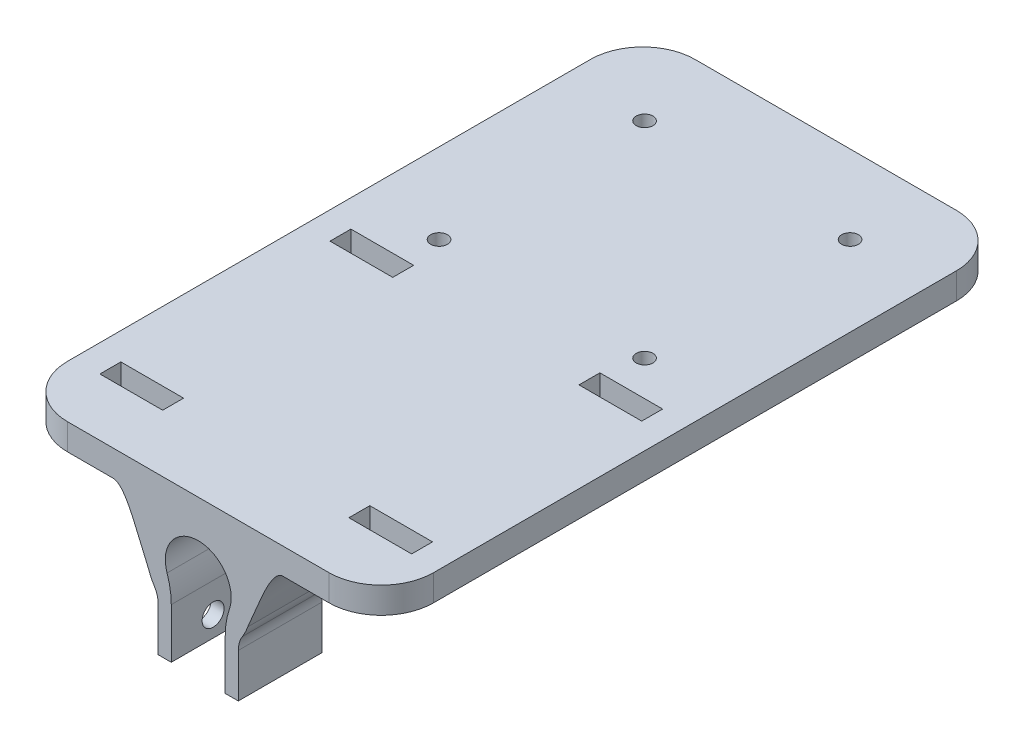
SolidWorks part; units mm, degrees
ref_plane "Front Plane" through (0, 0, 0) normal (0, 0, 1) x (1, 0, 0)
ref_plane "Top Plane" through (0, 0, 0) normal (0, 1, 0) x (1, 0, 0)
ref_plane "Right Plane" through (0, 0, 0) normal (1, 0, 0) x (0, 0, -1)
sketch "Sketch3" plane through (0, 0, 0) normal (0, 0, 1) x (1, 0, 0)
  line L0 (0, 11) -> (0, 0) construction
  line L1 (-35, 13.5) -> (35, 13.5)
  line L2 (-35, 13.5) -> (-35, 8.5)
  line L3 (-35, 8.5) -> (35, 8.5)
  line L4 (35, 13.5) -> (35, 8.5)
  line L5 (-35, 13.5) -> (35, 8.5) construction
  line L6 (-35, 8.5) -> (35, 13.5) construction
  point P0 (0, 11)
  dimension "D1" = 5
  dimension "D2" = 70
  dimension "D3" = 11
extrude "Boss-Extrude2" add sketch "Sketch3" along normal blind 120 from offset 10
sketch "Sketch1" plane through (0, 0, 0) normal (0, 0, 1) x (1, 0, 0)
  line L0 (-35, 8.5) -> (35, 8.5) construction
  line L1 (0, 0) -> (0, -9) construction
  line L2 (-16.0979, 8.5) -> (16.0979, 8.5)
  line L3 (0, 0) -> (-7.6604, -6.4279) construction
  line L5 (5.1604, -16.4279) -> (5.1604, -6.8736)
  line L6 (-6.1604, -16.4279) -> (-5.1604, -16.4279)
  line L7 (-6.1604, -16.4279) -> (-7.6604, -16.4279)
  line L8 (-5.1604, -16.4279) -> (-5.1604, -6.8736)
  line L9 (-7.6604, -16.4279) -> (-7.6604, -8.0444)
  line L10 (6.1604, -16.4279) -> (7.6604, -16.4279)
  line L11 (6.1604, -16.4279) -> (5.1604, -16.4279)
  line L12 (7.6604, -16.4279) -> (7.6604, -8.0444)
  arc A0 (5.9629, -2.033) -> (-5.9629, -2.033) centre (0, 0) ccw
  arc A1 (8.4403, -5.363) -> (9.4524, -3.2639) centre (0, 0) ccw
  arc A2 (-7.6604, -8.0444) -> (-8.4403, -5.363) centre (-12.6604, -8.0444) ccw
  arc A3 (-5.1604, -6.8736) -> (-5.9629, -2.033) centre (-20.1604, -6.8736) ccw
  arc A4 (5.1604, -6.8736) -> (5.9629, -2.033) centre (20.1604, -6.8736) cw
  arc A5 (7.6604, -8.0444) -> (8.4403, -5.363) centre (12.6604, -8.0444) cw
  arc A6 (-9.4524, -3.2639) -> (-8.4403, -5.363) centre (0, 0) ccw
  spline S0 degree 3 poles (-16.0979, 8.5) (-13.7253, 8.1529) (-11.6393, 1.5666) (-9.4524, -3.2639) knots 0 0 0 0 1 1 1 1
  spline S1 degree 3 poles (16.0979, 8.5) (13.7253, 8.1529) (11.6393, 1.5666) (9.4524, -3.2639) knots 0 0 0 0 1 1 1 1
  point P18 (-5.1604, -3.6138)
  point P21 (5.1604, -3.6138)
  point P24 (7.6604, -6.4279)
  point P27 (-9.8515, -1.717)
  point P28 (9.4524, -3.2639)
  dimension "D1" = 12.6
  dimension "D2" = 20
  dimension "D6" = 1
  dimension "D3" = 5
  dimension "D4" = 15
  dimension "D10" = 15
  dimension "D11" = 5
  dimension "D5" = 50
  dimension "D7" = 1.5
  dimension "D8" = 10
  dimension "D9" = 12.814
extrude "Boss-Extrude3" add sketch "Sketch1" along normal blind 8 and the other way blind 8 from offset 18
ref_plane "Plane4" through (0, 0, 70) normal (0, 0, 1) x (1, 0, 0)
sketch "Sketch4" plane through (-7.6604, 0, 0) normal (-1, 0, 0) x (0, 0, 1)
  line L0 (10, -8.0444) -> (26, -16.9992) construction
  line L1 (26, -8.0444) -> (26, -16.4279) construction
  circle A0 centre (18, -12.5218) radius 2.1
  dimension "D1" = 4.2
extrude "Cut-Extrude1" cut sketch "Sketch4" against normal blind 11
mirror "Mirror2" about plane through (0, 0, 70) normal (0, 0, 1) of "Boss-Extrude3", "Cut-Extrude1"
sketch "Sketch5" plane through (0, 13.5, 0) normal (0, 1, 0) x (1, 0, 0)
  line L0 (-16.6052, -70) -> (16.6052, -70) construction
  line L1 (-19.65, -25) -> (19.65, -25) construction
  line L2 (-19.65, -25) -> (-19.65, -64.3) construction
  line L3 (-19.65, -64.3) -> (19.65, -64.3) construction
  line L4 (19.65, -25) -> (19.65, -64.3) construction
  line L5 (-19.65, -25) -> (19.65, -64.3) construction
  line L6 (-19.65, -64.3) -> (19.65, -25) construction
  line L8 (35, -10) -> (-35, -130) construction
  line L9 (-35, -10) -> (-35, -130) construction
  line L10 (35, -130) -> (-35, -130) construction
  line L11 (35, -10) -> (-35, -10) construction
  line L18 (0, -10) -> (0, -130) construction
  circle A0 centre (19.65, -25) radius 1.6
  circle A1 centre (19.65, -64.3) radius 1.6
  circle A2 centre (-19.65, -64.3) radius 1.6
  circle A3 centre (-19.65, -25) radius 1.6
  point P0 (0, -70)
  point P23 (0, -44.65)
  dimension "D3" = 3.2
  dimension "D4" = 15
  dimension "D1" = 39.3
  dimension "D2" = 39.3
sketch "Sketch6" plane through (0, 13.5, 0) normal (0, 1, 0) x (1, 0, 0)
  line L0 (-16.6052, -70) -> (16.6052, -70) construction
  line L1 (-29.8063, -75) -> (-17.8063, -75)
  line L2 (-29.8063, -75) -> (-29.8063, -115) construction
  line L3 (-29.8063, -115) -> (-17.8063, -115)
  line L4 (29.8063, -75) -> (29.8063, -115) construction
  line L5 (-29.8063, -75) -> (29.8063, -115) construction
  line L6 (-29.8063, -115) -> (29.8063, -75) construction
  line L7 (-17.8063, -71) -> (-17.8063, -75)
  line L8 (17.8063, -71) -> (17.8063, -75)
  line L9 (-29.8063, -75) -> (-29.8063, -71)
  line L10 (-29.8063, -71) -> (-17.8063, -71)
  line L11 (29.8063, -71) -> (29.8063, -97.085)
  line L12 (-29.8063, -115) -> (-29.8063, -119)
  line L13 (-29.8063, -119) -> (-17.8063, -119)
  line L14 (29.8063, -119) -> (29.8063, -115)
  line L15 (29.8063, -75) -> (29.8063, -97.085)
  line L16 (17.8063, -75) -> (29.8063, -75)
  line L17 (17.8063, -71) -> (29.8063, -71)
  line L18 (17.8063, -115) -> (29.8063, -115)
  line L19 (17.8063, -119) -> (29.8063, -119)
  line L20 (-17.8063, -115) -> (-17.8063, -119)
  line L21 (17.8063, -115) -> (17.8063, -119)
  point P0 (0, -95)
  dimension "D1" = 40
  dimension "D2" = 12
  dimension "D3" = 25
  dimension "D4" = 12
  dimension "D5" = 4
  dimension "D6" = 4
fillet "Fillet1" radius 10 4 edges at (35, 11, 10) (35, 11, 130) (-35, 11, 130) (-35, 11, 10)
extrude "Cut-Extrude2" cut sketch "Sketch5" against normal blind 11
extrude "Cut-Extrude6" cut sketch "Sketch6" against normal up to next contours L11 L10 L9 L1 | L13 L14 L3 L12 | L18 L21 L19 L14 | L17 L8 L16 L11 region at (-23.8063, 13.5, 73) region at (-23.8063, 13.5, 117) region at (23.8063, 13.5, 73) region at (23.8063, 13.5, 117)
